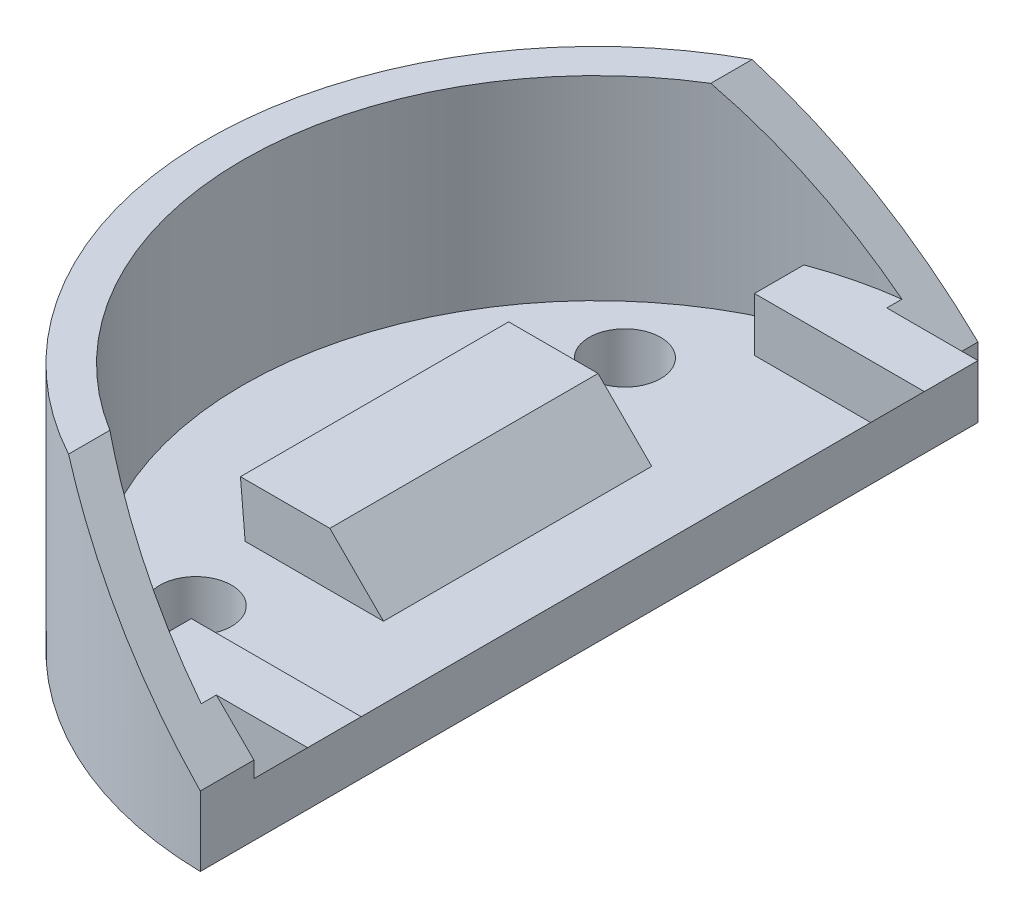
SolidWorks part; units mm, degrees
material "ABS"
ref_plane "Front Plane" through (0, 0, 0) normal (0, 0, 1) x (1, 0, 0)
ref_plane "Top Plane" through (0, 0, 0) normal (0, 1, 0) x (1, 0, 0)
ref_plane "Right Plane" through (0, 0, 0) normal (1, 0, 0) x (0, 0, -1)
sketch "Sketch1" plane through (0, 0, 0) normal (0, 1, 0) x (1, 0, 0)
  line L0 (-0.4821, 27.6183) -> (0, 0) construction
  line L1 (0, 0) -> (-0.4821, -27.6183) construction
  line L2 (0, 0) -> (-27.6225, 0) construction
  line L3 (-0.4821, 27.6183) -> (-0.4821, -27.6183)
  circle A0 centre (0, 0) radius 27.6225 construction
  arc A1 (-0.4821, 27.6183) -> (-0.4821, -27.6183) centre (0, 0) ccw
  circle A2 centre (-13.1821, 15.24) radius 2.54
  circle A3 centre (-13.1821, -15.24) radius 2.54
  arc A4 (-0.4821, 25.0783) -> (-0.4821, -25.0783) centre (0, 0) ccw
  point P13 (0, 0)
  dimension "D1" = 55.245
  dimension "D2" = 89
  dimension "D3" = 89
  dimension "D4" = 2.54
extrude "base" add sketch "Sketch1" along normal blind 3.81 contours A4 L3 A1 | L3 A4 A3 A2 region at (-1.0975, 0, -26.3483) region at (-10.8066, 0, 0)
sketch "Sketch2" plane through (0, 3.81, 0) normal (0, 1, 0) x (1, 0, 0)
  line L0 (0, 0) -> (-5.5621, 0) construction
  line L1 (-5.5621, 9.525) -> (-15.7221, 9.525)
  line L2 (-5.5621, 9.525) -> (-5.5621, -9.525)
  line L3 (-5.5621, -9.525) -> (-15.7221, -9.525)
  line L4 (-15.7221, 9.525) -> (-15.7221, -9.525)
  line L6 (4.5979, 23.8083) -> (-8.7371, 23.8083) construction
  line L7 (-0.4821, 27.6183) -> (-0.4821, -27.6183) construction
  line L8 (4.5979, 23.8083) -> (4.5979, 19.9983)
  line L9 (4.5979, 19.9983) -> (-8.7371, 19.9983)
  line L10 (-8.7371, 23.8083) -> (-8.7371, 19.9983)
  line L14 (4.5979, 23.8083) -> (-0.4821, 23.8083)
  line L15 (-0.4821, 23.8083) -> (-0.4821, 27.6183)
  line L16 (-0.4821, 27.6183) -> (-8.7371, 26.2043)
  line L17 (-8.7371, 26.2043) -> (-8.7371, 23.8083)
  line L18 (-0.4821, -27.6183) -> (-8.7371, -26.2043)
  line L19 (-0.4821, -23.8083) -> (-0.4821, -27.6183)
  line L20 (4.5979, -23.8083) -> (-0.4821, -23.8083)
  line L21 (4.5979, -23.8083) -> (4.5979, -19.9983)
  line L22 (4.5979, -19.9983) -> (-8.7371, -19.9983)
  line L23 (-8.7371, -23.8083) -> (-8.7371, -19.9983)
  line L24 (-8.7371, -26.2043) -> (-8.7371, -23.8083)
  arc A1 (-0.4821, 27.6183) -> (-0.4821, -27.6183) centre (0, 0) ccw construction
  point P4 (-5.5621, 0)
  dimension "D1" = 19.05
  dimension "D2" = 10.16
  dimension "D3" = 5.08
  dimension "D4" = 3.81
  dimension "D5" = 3.81
  dimension "D6" = 5.08
  dimension "D7" = 8.255
extrude "latch" add sketch "Sketch2" along normal blind 3.81 contours L2 L1 L4 L3 | L8 L9 L10 L17 L16 L15 L14 | L18 L24 L23 L22 L21 L20 L19
sketch "Sketch3" plane through (0, 3.81, 0) normal (0, 1, 0) x (1, 0, 0)
  line L0 (-0.4821, 19.9983) -> (-0.4821, -19.9983) construction
  line L1 (-0.4821, -25.0783) -> (-0.4821, -27.6183)
  line L2 (-0.4821, 27.6183) -> (-0.4821, 25.0783)
  arc A0 (-0.4821, 27.6183) -> (-0.4821, -27.6183) centre (0, 0) ccw
  arc A1 (-0.4821, 25.0783) -> (-0.4821, -25.0783) centre (0, 0) ccw
  dimension "D1" = 2.54
extrude "shell_extrude" add sketch "Sketch3" along normal blind 13.843
chamfer "alignment_stick_slope" distance 5.08 angle 45 2 edges at (4.5979, 3.81, -21.9033) (4.5979, 3.81, 21.9033)
sketch "Sketch4" plane through (0, 0, -9.525) normal (0, 0, -1) x (-1, 0, 0)
  line L0 (5.5621, 3.81) -> (9.3721, 7.62)
  line L1 (5.5621, 7.62) -> (15.7221, 7.62) construction
  line L2 (9.3721, 7.62) -> (15.7221, 7.62)
  line L3 (15.7221, 7.62) -> (15.3887, 3.81)
  line L4 (5.5621, 3.81) -> (15.7221, 3.81) construction
  line L5 (15.3887, 3.81) -> (5.5621, 3.81)
  line L6 (5.5621, 3.81) -> (5.5621, 7.62)
  line L7 (5.5621, 7.62) -> (9.3721, 7.62)
  line L8 (15.7221, 7.62) -> (15.7221, 3.81)
  line L9 (15.7221, 3.81) -> (15.3887, 3.81)
  line M6 (5.5621, 3.81) -> (15.7221, 3.81)
  line M7 (15.7221, 3.81) -> (15.7221, 7.62)
  line M8 (15.7221, 7.62) -> (5.5621, 7.62)
  line M9 (5.5621, 7.62) -> (5.5621, 3.81)
  dimension "D1" = 45
  dimension "D2" = 5
extrude "Cut-Extrude1" cut sketch "Sketch4" against normal up to surface (19.05 mm away) contours L0 M9 M8 | L3 M7 M6 region at (-6.8321, 6.35, -9.525) region at (-15.611, 5.08, -9.525) up to face at (-10.6421, 5.715, 9.525)
chamfer "Chamfer1" distance 12.7 angle 45 2 edges at (-0.4821, 17.653, -26.3483) (-0.4821, 17.653, 26.3483)
